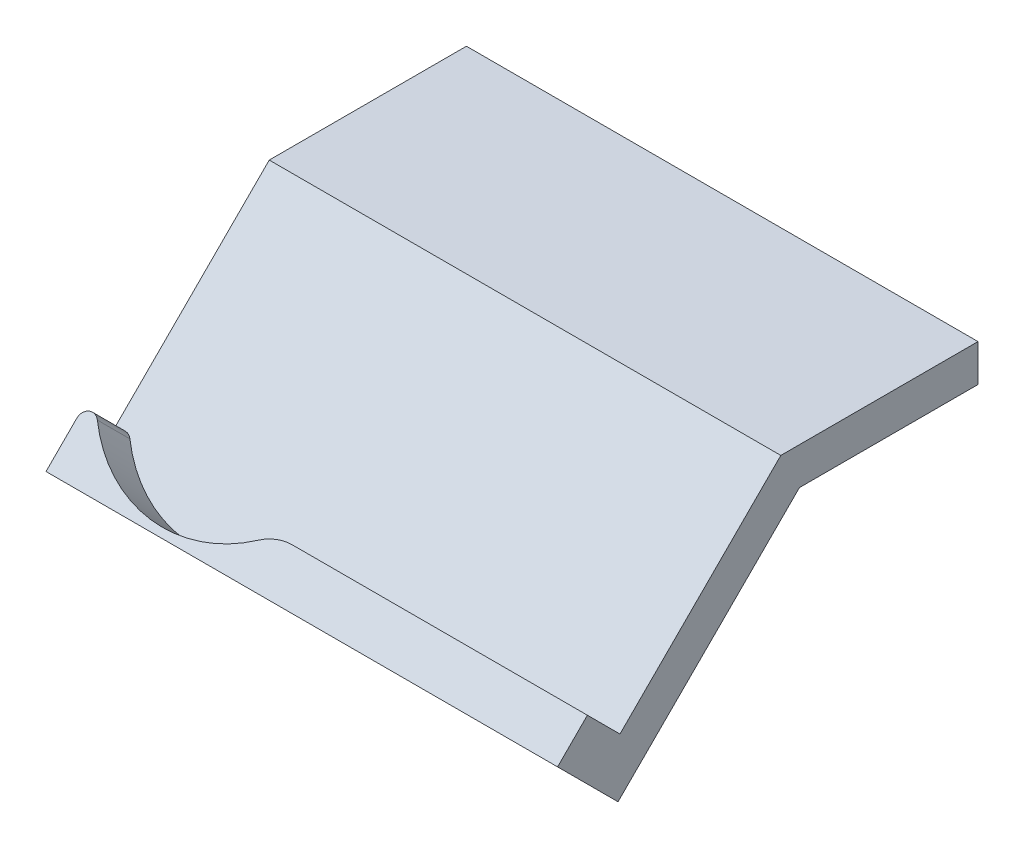
SolidWorks part; units mm, degrees
ref_plane "Front Plane" through (0, 0, 0) normal (0, 0, 1) x (1, 0, 0)
ref_plane "Top Plane" through (0, 0, 0) normal (0, 1, 0) x (1, 0, 0)
ref_plane "Right Plane" through (0, 0, 0) normal (1, 0, 0) x (0, 0, -1)
sketch "Sketch1" plane through (0, 0, 0) normal (0, 1, 0) x (1, 0, 0)
  line L1 (0, 28.5) -> (55, 28.5)
  line L2 (0, 28.5) -> (0, 0)
  line L3 (0, 0) -> (55, 0)
  line L4 (55, 28.5) -> (55, 0)
  dimension "D1" = 55
  dimension "D2" = 28.5
extrude "Boss-Extrude1" add sketch "Sketch1" along normal blind 50 contours L2 L3 L4 L1
sketch "Sketch4" plane through (55, 0, 0) normal (1, 0, 0) x (0, 0, -1)
  line L0 (28.5, 0) -> (0, 0) construction
  line L1 (-29.3553, 41.3553) -> (6, 76.7107)
  line L2 (-29.3553, 41.3553) -> (6, 6)
  line L3 (6, 6) -> (41.3553, 41.3553)
  line L4 (6, 76.7107) -> (41.3553, 41.3553)
  line L5 (0, 50) -> (0, 0) construction
  dimension "D1" = 50
  dimension "D2" = 50
  dimension "D3" = 6
  dimension "D4" = 6
extrude "Cut-Extrude1" cut sketch "Sketch4" against normal blind 50
sketch "Sketch5" plane through (55, 0, 0) normal (1, 0, 0) x (0, 0, -1)
  line L0 (0, 12) -> (0, 0) construction
  line L1 (-11.6421, 9.5) -> (-4.5711, 16.5711)
  line L2 (-11.6421, 9.5) -> (-4.5711, 2.4289)
  line L3 (-4.5711, 2.4289) -> (2.5, 9.5)
  line L4 (-4.5711, 16.5711) -> (2.5, 9.5)
  line L5 (0, 12) -> (6, 6) construction
  dimension "D1" = 10
  dimension "D2" = 10
  dimension "D3" = 2.5
extrude "Cut-Extrude2" cut sketch "Sketch5" against normal through all
sketch "Sketch12" plane through (55, 0, 0) normal (1, 0, 0) x (0, 0, -1)
  line L0 (2.5, 9.5) -> (6, 6)
  line L1 (6, 6) -> (6.7071, 6.7071)
  line L2 (6, 6) -> (28.5, 28.5) construction
  line L3 (6.7071, 6.7071) -> (3.2071, 10.2071)
  line L4 (3.2071, 10.2071) -> (2.5, 9.5)
  dimension "D1" = 1
extrude "Boss-Extrude2" add sketch "Sketch12" against normal through all contours L3 L4 L0 L1
sketch "Sketch6" plane through (0, 0, 0) normal (0, 0.7071, 0.7071) x (1, 0, 0)
  line L0 (55, 4.9497) -> (0, 4.9497) construction
  line L3 (0, 55.5079) -> (0, 35.3553) construction
  circle A0 centre (12, 19.4497) radius 13.75
  dimension "D1" = 27.5
  dimension "D2" = 14.5
  dimension "D3" = 12
extrude "Cut-Extrude3" cut sketch "Sketch6" along normal through all
ref_axis "Axis2" through (12, 34.8672, 7.3611) along (0, -0.7071, -0.7071)
sketch "Sketch7" plane through (55, 0, 0) normal (1, 0, 0) x (0, 0, -1)
  line L0 (0, 7) -> (5.5063, 12.5063)
  line L1 (18.4998, 18.4998) -> (9.0063, 9.0063) construction
  line L2 (5.5063, 12.5063) -> (9.0063, 9.0063)
  line L3 (9.0063, 9.0063) -> (57, 57)
  line L4 (57, 57) -> (25.4084, 57)
  line L5 (25.4084, 57) -> (0, 57)
  line L6 (0, 57) -> (0, 7)
  line L7 (9.0063, 9.0063) -> (0, 18.0127) construction
  line L8 (6.7071, 6.7071) -> (28.5, 28.5) construction
  dimension "D1" = 50
extrude "Cut-Extrude4" cut sketch "Sketch7" against normal through all contours L5 L6 L0 L2 L3 L4
sketch "Sketch8" plane through (0, 0, 0) normal (0, 1, 0) x (1, 0, 0)
  line L0 (12, -7.3611) -> (12, 9.0686) construction
  line L3 (55, 28.5) -> (0, 28.5) construction
  circle A0 centre (25.75, 30) radius 6
  dimension "D1" = 12
  dimension "D3" = 1.5
  dimension "D2" = 13.75
extrude "Cut-Extrude5" cut sketch "Sketch8" along normal through all contours A0
pattern_linear "LPattern1" count 2 spacing 27.5 along (-1, 0, 0) of "Cut-Extrude5"
sketch "Sketch9" plane through (55, 0, 0) normal (1, 0, 0) x (0, 0, -1)
  line L0 (24, 24) -> (28.5, 24)
  line L1 (28.5, 28.5) -> (28.5, 0) construction
  line L2 (28.5, 24) -> (28.5, 28.5)
  line L3 (28.5, 28.5) -> (24, 24)
extrude "Cut-Extrude6" cut sketch "Sketch9" against normal through all
sketch "Sketch10" plane through (0, 0, 0) normal (0, 1, 0) x (1, 0, 0)
  line L0 (0, 24) -> (25.75, 24) construction
  line L1 (55, 24) -> (0, 24)
  line L2 (55, 24) -> (55, 28.5)
  line L3 (55, 28.5) -> (0, 28.5)
  line L4 (0, 24) -> (0, 28.5)
  line L5 (0, 24) -> (0, 9.0063) construction
extrude "Cut-Extrude7" cut sketch "Sketch10" along normal through all
fillet "Fillet5" radius 1 1 edges at (0, 10.7563, -7.2563) tangent propagation no
fillet "Fillet6" radius 5 1 edges at (21.4748, 8.4571, -4.9571)
sketch "Sketch16" plane through (55, 0, 0) normal (1, 0, 0) x (0, 0, -1)
  line L0 (24, 18) -> (6.5, 0.5)
  line L1 (24, 24) -> (24, 0) construction
  line L2 (6.5, 0.5) -> (0, 7)
  line L3 (0, 7) -> (0, 0)
  line L4 (0, 0) -> (24, 0)
  line L5 (24, 0) -> (24, 18)
  line L6 (6.7071, 6.7071) -> (24, 24) construction
  dimension "D1" = 6
extrude "Cut-Extrude8" cut sketch "Sketch16" against normal through all
sketch "Sketch17" plane through (0, 0, -24) normal (0, 0, -1) x (-1, 0, 0)
  line L1 (-55, 24) -> (0, 24)
  line L2 (-55, 24) -> (-55, 20)
  line L3 (-55, 20) -> (0, 20)
  line L4 (0, 24) -> (0, 20)
  dimension "D1" = 4
extrude "Boss-Extrude4" add sketch "Sketch17" along normal blind 21.2
sketch "Sketch18" plane through (55, 0, 0) normal (1, 0, 0) x (0, 0, -1)
  line L0 (15.25, 9.25) -> (30, 24)
  line L1 (24, 18) -> (6.5, 0.5) construction
  line L2 (45.2, 24) -> (24, 24) construction
  line L3 (30, 24) -> (24, 24)
  line L4 (24, 24) -> (12.25, 12.25)
  line L5 (6.7071, 6.7071) -> (24, 24) construction
  line L6 (12.25, 12.25) -> (15.25, 9.25)
extrude "Boss-Extrude5" add sketch "Sketch18" against normal up to surface (55 mm away) contours L0 L3 L4 L6 up to face at (0, 14.6232, -21.0677)
